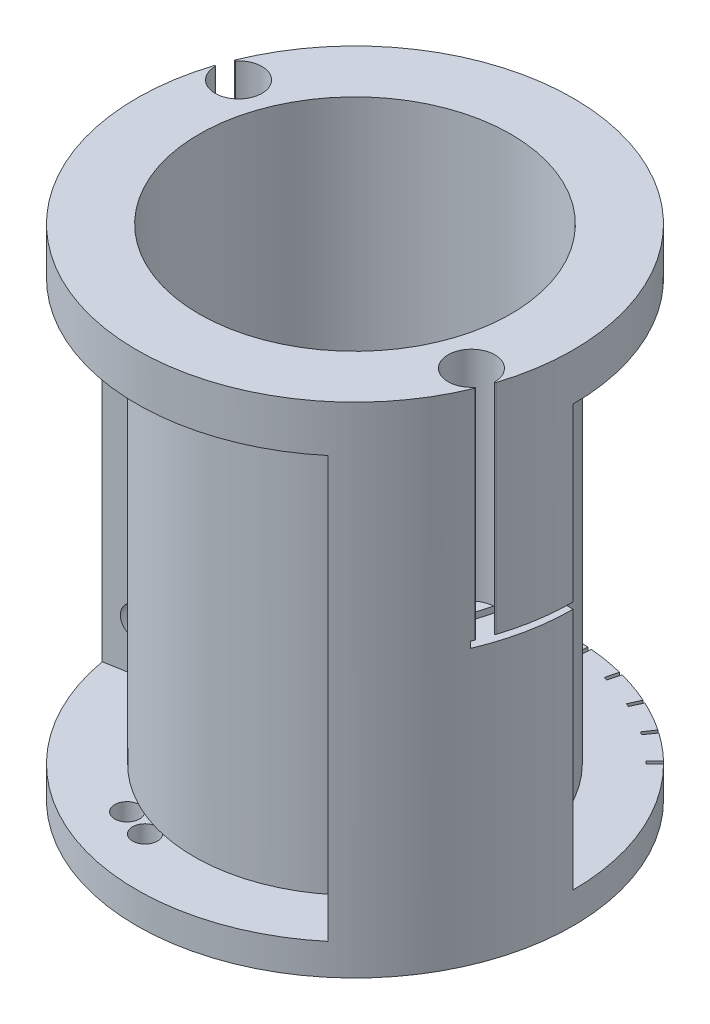
SolidWorks part; units mm, degrees
ref_plane "Front Plane" through (0, 0, 0) normal (0, 0, 1) x (1, 0, 0)
ref_plane "Top Plane" through (0, 0, 0) normal (0, 1, 0) x (1, 0, 0)
ref_plane "Right Plane" through (0, 0, 0) normal (1, 0, 0) x (0, 0, -1)
sketch "Sketch1" plane through (0, 0, 0) normal (0, 0, 1) x (1, 0, 0)
  line L0 (0, 0) -> (0, 127) construction
  line L1 (0, 0) -> (63.5, 0) construction
  line L2 (63.5, 0) -> (63.5, 203.2)
  line L3 (63.5, 203.2) -> (88.9, 203.2)
  line L4 (88.9, 203.2) -> (88.9, 0)
  line L5 (63.5, 0) -> (88.9, 0)
  dimension "D1" = 25.4
  dimension "D2" = 203.2
  dimension "D3" = 63.5
revolve "Revolve1" add sketch "Sketch1" angle 360 about L0
sketch "Sketch2" plane through (0, 0, 0) normal (0, 0, 1) x (1, 0, 0)
  line L0 (0, 0) -> (0, 12.7) construction
  line L1 (0, 12.7) -> (63.5, 12.7) construction
  line L2 (63.5, 12.7) -> (65.5, 12.7) construction
  line L3 (65.5, 12.7) -> (65.5, 184.15)
  line L4 (65.5, 184.15) -> (88.9, 184.15)
  line L5 (88.9, 0) -> (88.9, 203.2) construction
  line L6 (88.9, 184.15) -> (88.9, 12.7)
  line L7 (88.9, 12.7) -> (65.5, 12.7)
  dimension "D1" = 12.7
  dimension "D2" = 63.5
  dimension "D3" = 2
  dimension "D4" = 171.45
revolve "Cut-Revolve1" cut sketch "Sketch2" angle 140 about L0
ref_axis "Axis1" through (0, -7.62, 0) along (0, 1, 0)
ref_plane "Plane1" through (0, 0, 0) normal (0.6428, 0, -0.766) x (0, 1, 0)
ref_plane "Plane2" through (0, 0, 0) normal (-1, 0, 0) x (0, 1, 0)
ref_axis "Axis2" through (0, -1672.3363, 0) along (0, 1, 0)
sketch "Sketch5" plane through (0, 203.2, 0) normal (0, 1, 0) x (1, 0, 0)
  line L0 (0, 0) -> (-74.6, 27.1522) construction
  line L1 (0, 0) -> (-79.3877, 0) construction
  circle A0 centre (0, 0) radius 79.3877 construction
  circle A1 centre (-74.6, 27.1522) radius 9.525
  dimension "D1" = 19.05
  dimension "D2" = 158.7754
  dimension "D3" = 20
extrude "Cut-Extrude1" cut sketch "Sketch5" against normal blind 88.9
ref_axis "Axis3" through (0, 213.36, 0) along (0, -1, 0)
sketch "Sketch7" plane through (0, 0, 0) normal (0.6428, 0, -0.766) x (-0.766, 0, -0.6428)
  line L0 (88.9, 12.7) -> (88.9, 184.15) construction
  line L1 (88.9, 114.3) -> (76.2, 114.3)
  line L2 (88.9, 114.3) -> (88.9, 111.76)
  line L3 (88.9, 111.76) -> (76.2, 111.76)
  line L4 (76.2, 114.3) -> (76.2, 111.76)
  line L5 (88.9, 184.15) -> (65.5, 184.15) construction
  dimension "D1" = 2.54
  dimension "D2" = 12.7
  dimension "D3" = 69.85
revolve "Cut-Revolve3" cut sketch "Sketch7" angle 23 about axis through (0, 213.36, 0) along (0, -1, 0) reverse direction yes
fillet "Fillet2" radius 0.254 2 edges at (-83.3593, 158.75, -30.894) (-83.7152, 158.75, -29.9161)
ref_plane "Plane3" through (0, 0, 0) normal (-0.9397, 0, -0.342) x (-0.342, 0, 0.9397)
mirror "Mirror1" about plane through (0, 0, 0) normal (-0.9397, 0, -0.342) of "Fillet2", "Cut-Extrude1", "Cut-Revolve3"
sketch "Sketch12" plane through (0, 12.7, 0) normal (0, 1, 0) x (1, 0, 0)
  line L0 (0, 0) -> (23.8901, 65.6375) construction
  line L1 (0, 0) -> (29.5199, 63.3056)
  line L2 (0, 0) -> (18.0785, 67.4699)
  line L3 (0, 0) -> (-23.8901, -65.6375) construction
  line L4 (20.2022, 55.5052) -> (-20.2022, -55.5052) construction
  line L5 (0, 0) -> (-18.0785, -67.4699)
  line L6 (0, 0) -> (-29.5199, -63.3056)
  circle A0 centre (0, 0) radius 69.85 construction
  circle A3 centre (-29.5199, -63.3056) radius 5.08
  circle A4 centre (-18.0785, -67.4699) radius 5.08
  dimension "D1" = 139.7
  dimension "D4" = 10.16
  dimension "D3" = 5
sketch "Sketch15" plane through (0, 12.7, 0) normal (0, 1, 0) x (1, 0, 0)
  line L0 (0, 0) -> (30.4056, 83.5387) construction
  line L1 (59.2697, 59.2697) -> (62.8618, 62.8618)
  line L2 (58.2263, 60.2951) -> (61.7551, 63.9493)
  arc A0 (88.9, 0) -> (-68.1014, 57.1438) centre (0, 0) ccw construction
  arc A1 (62.8618, 62.8618) -> (61.7551, 63.9493) centre (0, 0) ccw
  arc A2 (59.2697, 59.2697) -> (58.2263, 60.2951) centre (0, 0) ccw
  arc A3 (88.9, 0) -> (-68.1014, 57.1438) centre (0, 0) ccw construction
  arc A4 (83.82, 0) -> (-64.2098, 53.8785) centre (0, 0) ccw construction
  dimension "D1" = 5.08
  dimension "D2" = 1
  dimension "D3" = 25
extrude "Cut-Extrude6" cut sketch "Sketch15" against normal up to surface (12.7 mm away) up to face at (0, 0, -88.9)
pattern_circular "CirPattern1" count 6 every 10 about axis through (0, 12.7, 0) along (0, -1, 0) of "Cut-Extrude6" reverse direction yes
extrude "Cut-Extrude7" cut sketch "Sketch12" against normal up to surface (12.7 mm away) contours A3 | A4 region at (-14.1623, 12.7, 64.4649) region at (-25.3566, 12.7, 60.6533) up to face at (0, 0, -63.5)
sketch "Sketch16" plane through (0, 0, 0) normal (-0.9397, 0, -0.342) x (-0.342, 0, 0.9397)
  line L0 (0, 0) -> (88.9, 0) construction
  line L1 (88.9, 0) -> (88.9, 12.7) construction
  line L2 (88.9, 0) -> (88.9, 203.2) construction
  line L3 (88.9, 12.7) -> (65.532, 12.7)
  line L4 (65.532, 12.7) -> (65.532, 184.15)
  line L5 (65.532, 184.15) -> (88.9, 184.15)
  line L6 (88.9, 184.15) -> (88.9, 12.7)
  dimension "D1" = 171.45
  dimension "D2" = 23.368
  dimension "D3" = 12.7
revolve "Cut-Revolve4" cut sketch "Sketch16" angle 60 about axis through (0, -7.62, 0) along (0, 1, 0) other way angle 60
sketch "Sketch17" plane through (0, 0, 0) normal (-0.9397, 0, -0.342) x (-0.342, 0, 0.9397)
  line L0 (0, 0) -> (76.2, 0) construction
  line L1 (76.2, 0) -> (76.2, 31.75) construction
  circle A0 centre (76.2, 31.75) radius 6.35
  dimension "D1" = 12.7
  dimension "D2" = 76.2
  dimension "D3" = 31.75
revolve "Cut-Revolve5" cut sketch "Sketch17" about axis through (0, 213.36, 0) along (0, -1, 0)
ref_plane "Plane4" through (88.9, 184.15, 0) normal (0, 0, 1) x (1, 0, 0)
ref_plane "Plane5" through (30.4056, 0, -83.5387) normal (0.342, 0, -0.9397) x (-0.9397, 0, -0.342)
